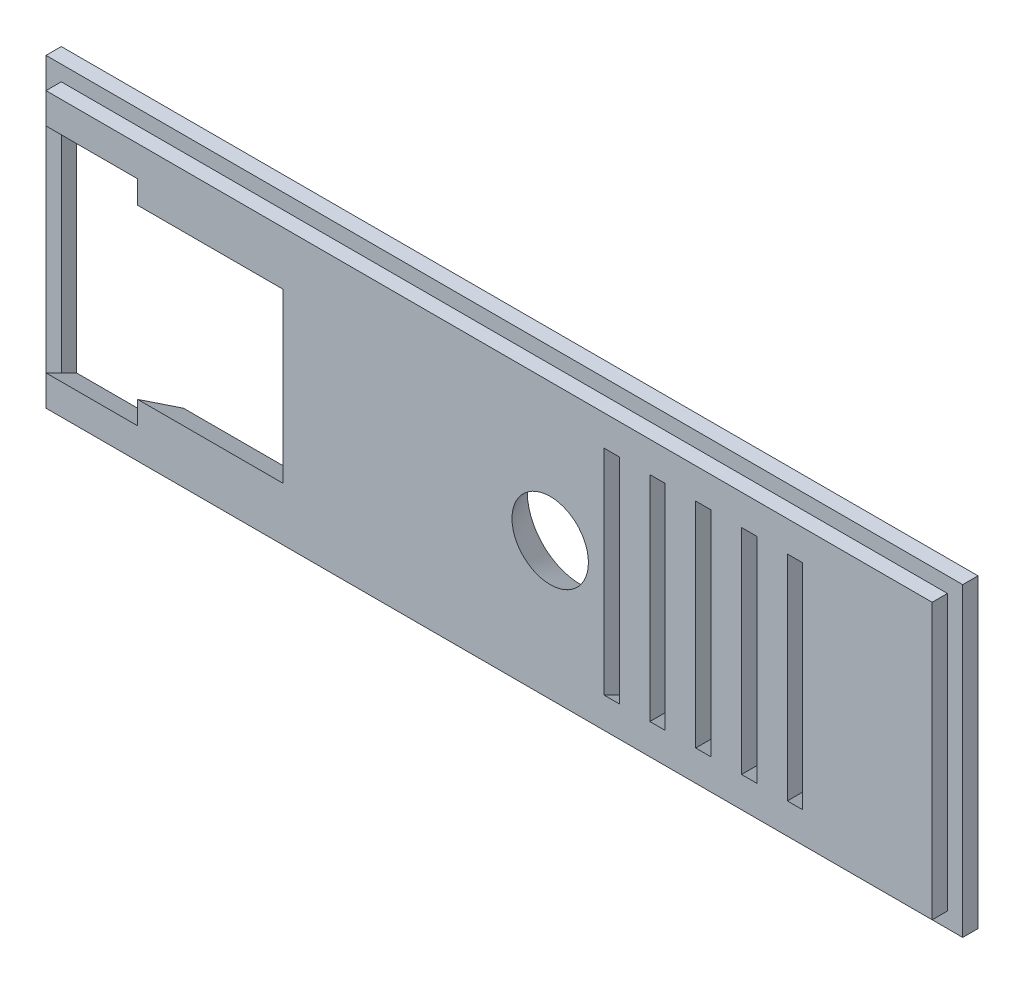
SolidWorks part; units mm, degrees
ref_plane "Front Plane" through (0, 0, 0) normal (0, 0, 1) x (1, 0, 0)
ref_plane "Top Plane" through (0, 0, 0) normal (0, 1, 0) x (1, 0, 0)
ref_plane "Right Plane" through (0, 0, 0) normal (1, 0, 0) x (0, 0, -1)
sketch "Sketch1" plane through (0, 0, 0) normal (0, 0, 1) x (1, 0, 0)
  line L0 (-30, 0) -> (30, 0) construction
  line L1 (-30, -10) -> (30, -10)
  line L2 (-30, -10) -> (-30, 10)
  line L3 (-30, 10) -> (30, 10)
  line L4 (30, -10) -> (30, 10)
  line L5 (0, 10) -> (0, -10) construction
  point P6 (0, 0)
  dimension "D1" = 20
  dimension "D2" = 60
extrude "Boss-Extrude1" add sketch "Sketch1" along normal blind 1
sketch "Sketch2" plane through (0, 0, 1) normal (0, 0, 1) x (1, 0, 0)
  line L0 (-29, 9) -> (-29, -9)
  line L1 (-29, -9) -> (29, -9)
  line L2 (29, -9) -> (29, 9)
  line L3 (29, 9) -> (-29, 9)
extrude "Boss-Extrude2" add sketch "Sketch2" along normal blind 1
sketch "Sketch4" plane through (0, 0, 0) normal (0, 0, -1) x (-1, 0, 0)
  line L0 (30, 0) -> (29, 0) construction
  line L1 (30, 10) -> (30, -10) construction
  line L2 (-30, -10) -> (-30, 10) construction
  line L3 (30, 0) -> (29, 0) construction
  line L4 (13.5, 0) -> (13.5, 5.5) construction
  line L5 (13.5, 5.5) -> (13.5, 10) construction
  line L6 (-30, 10) -> (30, 10) construction
  line L7 (13.5, -5.5) -> (23, -5.5)
  line L8 (13.5, 5.5) -> (23, 5.5)
  line L9 (13.5, 5.5) -> (13.5, -5.5)
  line L11 (29, 5.5) -> (29, -5.5)
  line L12 (13.5, 0) -> (-30, 0) construction
  line L13 (23, 5.5) -> (23, 7)
  line L14 (23, 7) -> (29, 7)
  line L15 (29, 7) -> (29, 5.5)
  line L16 (29, -7) -> (29, -5.5)
  line L17 (23, -7) -> (29, -7)
  line L18 (23, -5.5) -> (23, -7)
  line L19 (-30, 0) -> (-4, 0) construction
  line L20 (-20.5221, 7) -> (-20.5221, -7)
  line L21 (-20.5221, -7) -> (-19.5221, -7)
  line L22 (-19.5221, -7) -> (-19.5221, 7)
  line L23 (-19.5221, 7) -> (-20.5221, 7)
  line L24 (-17.5221, 7) -> (-17.5221, -7)
  line L25 (-17.5221, -7) -> (-16.5221, -7)
  line L26 (-16.5221, -7) -> (-16.5221, 7)
  line L27 (-16.5221, 7) -> (-17.5221, 7)
  line L28 (-14.5221, 7) -> (-14.5221, -7)
  line L29 (-14.5221, -7) -> (-13.5221, -7)
  line L30 (-13.5221, -7) -> (-13.5221, 7)
  line L31 (-13.5221, 7) -> (-14.5221, 7)
  line L32 (-11.5221, 7) -> (-11.5221, -7)
  line L33 (-11.5221, -7) -> (-10.5221, -7)
  line L34 (-10.5221, -7) -> (-10.5221, 7)
  line L35 (-10.5221, 7) -> (-11.5221, 7)
  line L36 (-8.5221, 7) -> (-8.5221, -7)
  line L37 (-8.5221, -7) -> (-7.5221, -7)
  line L38 (-7.5221, -7) -> (-7.5221, 7)
  line L39 (-7.5221, 7) -> (-8.5221, 7)
  circle A0 centre (-4, 0) radius 2.5
  dimension "D5" = 1
  dimension "D1" = 4.5
  dimension "D2" = 1
  dimension "D3" = 1.5
  dimension "D4" = 6
  dimension "D6" = 5
extrude "Cut-Extrude2" cut sketch "Sketch4" against normal blind 4
ref_plane "Plane1" through (20.5221, 7, 0) normal (0, -1, 0) x (-1, 0, 0)
chamfer "Chamfer2" distance 1 distance2 2 26 edges at (8.0221, -7, 0) (8.5221, 0, 0) (8.0221, 7, 0) (11.0221, 7, 0) (10.5221, 0, 0) (11.0221, -7, 0) (11.5221, 0, 0) (13.5221, 0, 0) (14.0221, -7, 0) (14.5221, 0, 0) (14.0221, 7, 0) (17.0221, 7, 0) (16.5221, 0, 0) (17.0221, -7, 0) (17.5221, 0, 0) (20.0221, 7, 0) (20.0221, -7, 0) (19.5221, 0, 0) (1.5, 0, 0) (-26, 7, 0) (-23, 6.25, 0) (-18.25, 5.5, 0) (-13.5, 0, 0) (-18.25, -5.5, 0) (-23, -6.25, 0) (-26, -7, 0) first distance on face at (-22.125, 0, 0)
